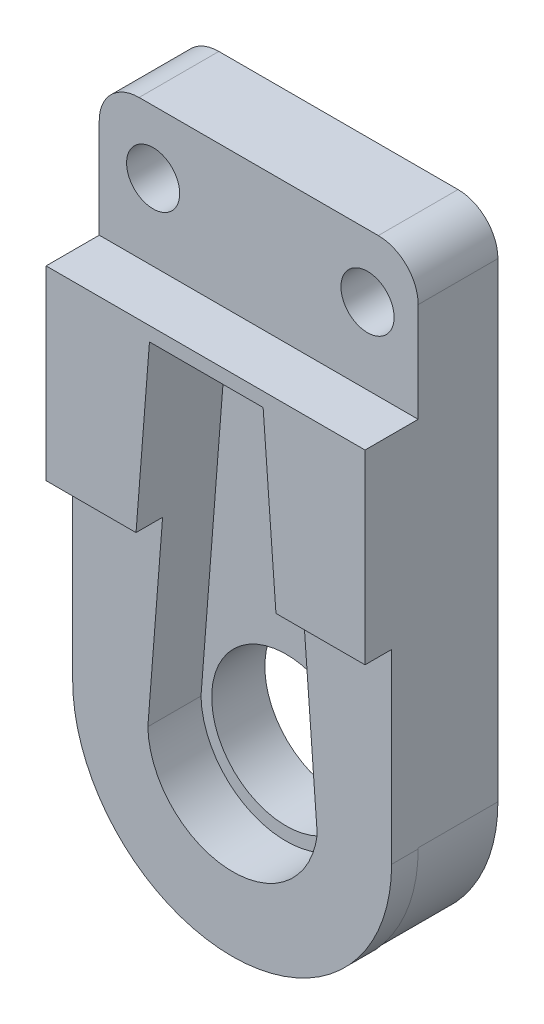
SolidWorks part; units mm, degrees
ref_plane "Front Plane" through (0, 0, 0) normal (0, 0, 1) x (1, 0, 0)
ref_plane "Top Plane" through (0, 0, 0) normal (0, 1, 0) x (1, 0, 0)
ref_plane "Right Plane" through (0, 0, 0) normal (1, 0, 0) x (0, 0, -1)
other "Graphic1"
ref_plane "Plane1" through (0, 0, 5) normal (0, 0, 1) x (1, 0, 0)
sketch "Sketch1" plane through (0, 0, 5) normal (0, 0, 1) x (1, 0, 0)
  line L1 (-60.0277, 110.2557) -> (-48.0277, 110.2557)
  line L2 (-60.0277, 110.2557) -> (-60.0277, 85.0557)
  line L3 (-60.0277, 85.0557) -> (-48.0277, 85.0557)
  line L4 (-48.0277, 110.2557) -> (-48.0277, 85.0557)
  dimension "D1" = 12
  dimension "D2" = 25.2
extrude "Boss-Extrude1" add sketch "Sketch1" along normal blind 3
fillet "Fillet1" radius 6 2 edges at (-48.0277, 85.0557, 6.5) (-60.0277, 85.0557, 6.5)
sketch "Sketch3" plane through (0, 0, 8) normal (0, 0, 1) x (1, 0, 0)
  line L1 (-60.0277, 105.018) -> (-48.0277, 105.018)
  line L2 (-60.0277, 105.018) -> (-60.0277, 85.018)
  line L3 (-60.0277, 85.018) -> (-48.0277, 85.018)
  line L4 (-48.0277, 105.018) -> (-48.0277, 85.018)
  dimension "D1" = 12
  dimension "D2" = 20
extrude "Boss-Extrude2" add sketch "Sketch3" along normal blind 2
fillet "Fillet2" radius 6 2 edges at (-48.0277, 85.018, 9) (-60.0277, 85.018, 9)
sketch "Sketch4" plane through (0, 0, 10) normal (0, 0, 1) x (1, 0, 0)
  line L0 (-56.1384, 104.486) -> (-51.8616, 104.486)
  line L1 (-51.8616, 104.486) -> (-50.8249, 90.587)
  line L2 (-56.1384, 104.486) -> (-57.1992, 90.915)
  arc A0 (-57.1992, 90.915) -> (-50.8249, 90.587) centre (-54, 90.9854) ccw
  point P10 (-50.8249, 90.3964)
extrude "Cut-Extrude1" cut sketch "Sketch4" against normal mid plane 6
sketch "Sketch5" plane through (0, 0, 7) normal (0, 0, 1) x (1, 0, 0)
  circle A0 centre (-53.9974, 91.082) radius 2.8
extrude "Cut-Extrude2" cut sketch "Sketch5" against normal through all
sketch "Sketch6" plane through (0, 0, 8) normal (0, 0, 1) x (1, 0, 0)
  circle A0 centre (-57.9999, 107.8868) radius 1
  circle A1 centre (-49.9341, 107.8868) radius 1
extrude "Cut-Extrude3" cut sketch "Sketch6" against normal through all
sketch "Sketch7" plane through (0, 0, 10) normal (0, 0, 1) x (1, 0, 0)
  line L0 (-60.0277, 105.018) -> (-60.0277, 91.018) construction
  line L1 (-60.0277, 98.018) -> (-47.6238, 98.018)
  line L2 (-60.0277, 98.018) -> (-60.0277, 84.6343)
  line L3 (-60.0277, 84.6343) -> (-47.6238, 84.6343)
  line L4 (-47.6238, 98.018) -> (-47.6238, 84.6343)
  point P6 (-31.3417, 100.5023)
extrude "Cut-Extrude4" cut sketch "Sketch7" against normal blind 1
fillet "Fillet3" radius 1.5 2 edges at (-60.0277, 110.2557, 6.5) (-48.0277, 110.2557, 6.5)
